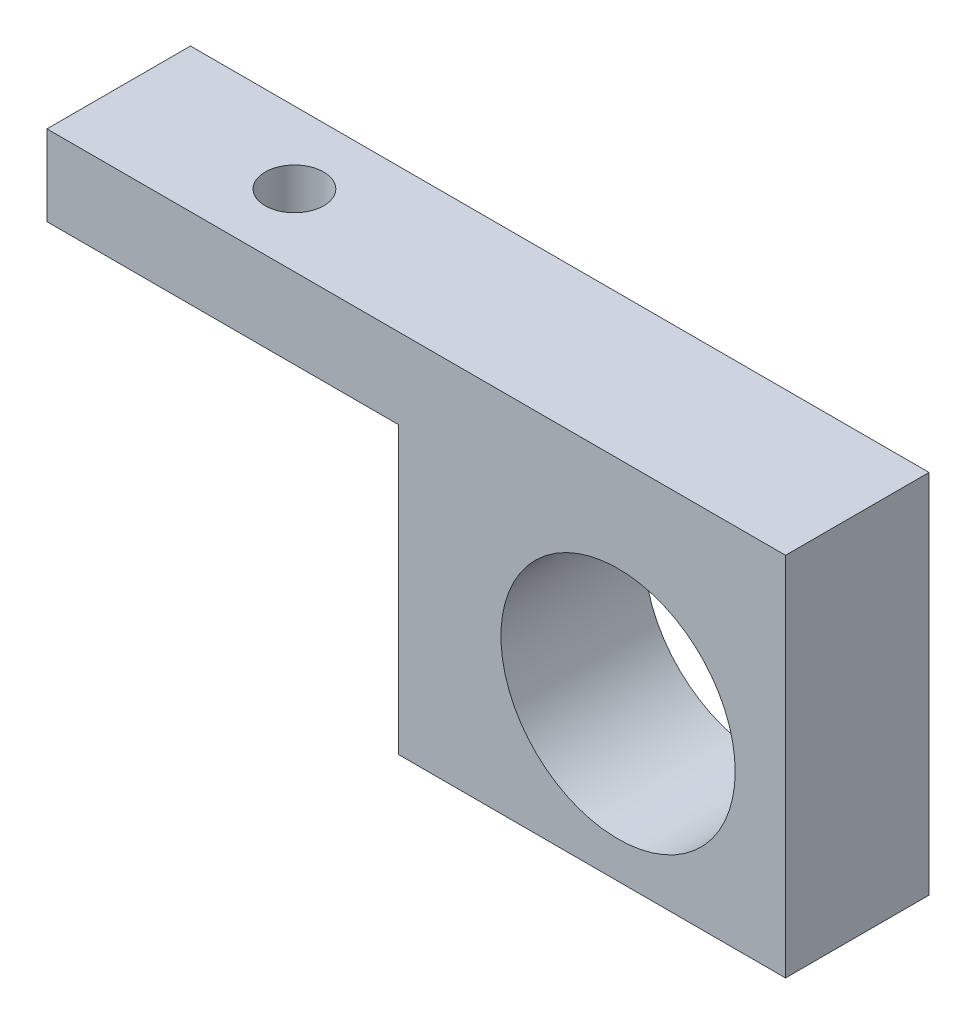
SolidWorks part; units mm, degrees
material "ABS"
ref_plane "Front Plane" through (0, 0, 0) normal (0, 0, 1) x (1, 0, 0)
ref_plane "Top Plane" through (0, 0, 0) normal (0, 1, 0) x (1, 0, 0)
ref_plane "Right Plane" through (0, 0, 0) normal (1, 0, 0) x (0, 0, -1)
sketch "Sketch1" plane through (0, 0, 0) normal (0, 0, 1) x (1, 0, 0)
  line L0 (-24, 15) -> (0, 15)
  line L1 (0, 15) -> (0, 0)
  line L2 (0, 0) -> (93, 0)
  line L3 (93, 0) -> (93, 102.7)
  line L4 (93, 102.7) -> (0, 102.7)
  line L5 (0, 102.7) -> (0, 30)
  line L6 (0, 30) -> (-24, 30)
  line L7 (-24, 30) -> (-24, 15)
  circle A0 centre (15, 10.5) radius 8
  circle A1 centre (70, 72) radius 11
  circle A2 centre (15, 10.5) radius 11
  dimension "D1" = 15
  dimension "D10" = 16
  dimension "D11" = 22
  dimension "D12" = 22
  dimension "D2" = 24
  dimension "D3" = 72.7
  dimension "D4" = 15
  dimension "D5" = 15
  dimension "D6" = 10.5
  dimension "D7" = 82.5061
  dimension "D8" = 72
  dimension "D9" = 93
extrude "Boss-Extrude1" add sketch "Sketch1" along normal blind 4.8 contours A2 L2 L3 L4 L5 L6 L7 L0 L1 A1 | L2 A2 A0 region at (44.5238, 51.0418, 0) region at (8.6656, 19.1141, 0)
sketch "Sketch2" plane through (0, 0, 4.8) normal (0, 0, 1) x (1, 0, 0)
  line L0 (93, 0) -> (93, 102.7) construction
  line L1 (48.1786, 92.7632) -> (93, 92.7632)
  line L2 (48.1786, 92.7632) -> (48.1786, 52.666)
  line L3 (48.1786, 52.666) -> (93, 52.666)
  line L4 (93, 92.7632) -> (93, 52.666)
  line L5 (48.1786, 92.7632) -> (93, 52.666) construction
  line L6 (48.1786, 52.666) -> (93, 92.7632) construction
  circle A0 centre (70, 72) radius 11
  circle A1 centre (70, 72) radius 4.15
  point P8 (70.5893, 72.7146)
  line M4 (93, 0) -> (93, 102.7)
  circle M10 centre (70, 72) radius 11
  dimension "D1" = 22
  dimension "D2" = 8.3
extrude "Boss-Extrude2" add sketch "Sketch2" along normal blind 8.2 contours L2 L3 L1 M4 M10 region at (70.5893, 92.1618, 4.8)
sketch "Sketch3" plane through (0, 0, 4.8) normal (0, 0, 1) x (1, 0, 0)
  line L1 (-24, 15) -> (0, 15)
  line L2 (-24, 15) -> (-24, 30)
  line L3 (-24, 30) -> (0, 30)
  line L4 (0, 15) -> (0, 30)
  line L5 (-24, 15) -> (0, 30) construction
  line L6 (-24, 30) -> (0, 15) construction
  line L7 (0, 0) -> (93, 0)
  line L8 (0, 0) -> (0, 52.666)
  line L9 (0, 52.666) -> (93, 52.666)
  line L10 (93, 0) -> (93, 52.666)
  line L11 (0, 0) -> (93, 52.666) construction
  line L12 (0, 52.666) -> (93, 0) construction
  circle A0 centre (15, 10.5) radius 8
  point P4 (-12, 22.5)
  point P11 (46.5, 26.333)
  circle M1 centre (15, 10.5) radius 8
  line M6 (0, 102.7) -> (0, 30)
  line M7 (0, 30) -> (-24, 30)
  line M8 (-24, 30) -> (-24, 15)
  line M9 (-24, 15) -> (0, 15)
  line M10 (0, 15) -> (0, 0)
  line M11 (0, 0) -> (93, 0)
  line M12 (93, 0) -> (93, 52.666)
  line M13 (93, 52.666) -> (48.1786, 52.666)
extrude "Boss-Extrude3" add sketch "Sketch3" along normal blind 5 contours L4 M9 M7 M8 | L9 L4 M6 M10 M11 M12 M13 M1 region at (-12, 22.5, 4.8) region at (47.8484, 27.0108, 4.8)
sketch "Sketch4" plane through (0, 83.2317, 0) normal (0, -1, 0) x (1, 0, 0)
  line L0 (0, 9.8) -> (0, 4.8) construction
  line L1 (0, 4.8) -> (48.1786, 4.8)
  line L2 (0, 4.8) -> (0, 45.3)
  line L3 (0, 45.3) -> (48.1786, 45.3)
  line L4 (48.1786, 4.8) -> (48.1786, 45.3)
  line L5 (0, 4.8) -> (48.1786, 45.3) construction
  line L6 (0, 45.3) -> (48.1786, 4.8) construction
  line L7 (0, 4.8) -> (48.1786, 4.8) construction
  line L8 (48.1786, 13) -> (48.1786, 9.8) construction
  line L9 (0, 0) -> (93, 0) construction
  line L10 (0, 45.3) -> (-5, 45.3)
  line L11 (0, 45.3) -> (0, 0)
  line L12 (0, 0) -> (-5, 0)
  line L13 (-5, 45.3) -> (-5, 0)
  line L14 (0, 45.3) -> (-5, 0) construction
  line L15 (0, 0) -> (-5, 45.3) construction
  circle A0 centre (13.9465, 30.3) radius 6.35
  circle A1 centre (13.9465, 23.3) radius 18.5
  circle A3 centre (29.4465, 23.3) radius 2
  circle A4 centre (21.6965, 9.8766) radius 2
  circle A5 centre (6.1965, 9.8766) radius 2
  point P10 (24.0893, 25.05)
  point P30 (-2.5, 22.65)
  arc M5 (5.039, 30.9329) -> (22.854, 30.9329) centre (13.9465, 30.3) ccw
  arc M7 (23.1854, 31.0672) -> (4.7077, 31.0672) centre (13.9465, 23.3) cw
  circle M9 centre (21.6965, 9.8766) radius 1.6
  circle M10 centre (6.1965, 9.8766) radius 1.6
  circle M11 centre (-1.5535, 23.3) radius 1.6
  circle M12 centre (6.1965, 36.7234) radius 1.6
  circle M13 centre (21.6965, 36.7234) radius 1.6
  circle M15 centre (27.3699, 31.05) radius 2.1
  circle M16 centre (0.5231, 31.05) radius 2.1
  circle M17 centre (13.9465, 7.8) radius 2.1
  circle M19 centre (13.9465, 23.3) radius 18.5
  dimension "D1" = 12.7
  dimension "D2" = 15
  dimension "D3" = 4
  dimension "D4" = 4
  dimension "D5" = 4
  dimension "D6" = 5
  dimension "D7" = 0
extrude "Boss-Extrude4" add sketch "Sketch4" along normal blind 5 contours L1 L4 L3 M19 | A0 L3 L2 A5 A4 A3 M12 M19 M16 M11 M13 M17 M15 M5 M7 | M5 M7 | M17 | A4 M9 | M9 | M10 | A5 M10 | M15 | L2 M16 | L2 L1 M19 region at (3.3557, 83.2317, 6.6306) region at (34.3643, 83.2317, 27.4815) region at (15.1399, 83.2317, 22.3686) region at (1.1393, 83.2317, 31.05) region at (19.7531, 83.2317, 9.8766) region at (4.2531, 83.2317, 9.8766) region at (21.6965, 83.2317, 9.8766) region at (6.1965, 83.2317, 9.8766) region at (27.3699, 83.2317, 31.05) region at (13.9465, 83.2317, 7.8)
sketch "Sketch5" plane through (48.1786, 0, 0) normal (1, 0, 0) x (0, 0, -1)
  line L0 (-45.3, 83.2317) -> (-13, 92.7632)
  line L1 (-13, 92.7632) -> (-4.8, 92.7632)
  line L2 (-4.8, 92.7632) -> (-4.8, 78.2317)
  line L3 (-4.8, 78.2317) -> (-45.3, 78.2317)
  line L4 (-45.3, 78.2317) -> (-45.3, 83.2317)
extrude "Boss-Extrude5" add sketch "Sketch5" against normal blind 5
sketch "Sketch6" plane through (0, 0, 4.8) normal (0, 0, 1) x (1, 0, 0)
  line L0 (0, 78.2317) -> (0, 52.666) construction
  line L1 (0, 78.2317) -> (48.1786, 78.2317)
  line L2 (0, 78.2317) -> (0, 52.666)
  line L3 (0, 52.666) -> (48.1786, 52.666)
  line L4 (48.1786, 78.2317) -> (48.1786, 52.666)
  line L5 (0, 78.2317) -> (48.1786, 52.666) construction
  line L6 (0, 52.666) -> (48.1786, 78.2317) construction
  line L7 (0, 78.2317) -> (48.1786, 78.2317) construction
  point P4 (24.0893, 65.4489)
extrude "Boss-Extrude6" add sketch "Sketch6" along normal up to surface (5 mm away) up to face at (20.6865, 27.5553, 9.8)
ref_plane "Plane1" through (3.9877, 7.5909, 34.4544) normal (0.9262, 0.2454, -0.2862) x (0.0581, -0.8429, -0.5349)
sketch "Sketch8" plane through (0, 30, 0) normal (0, 1, 0) x (1, 0, 0)
  line L0 (0, 0) -> (-24, -9.8)
  line L1 (-24, -9.8) -> (-24, 0)
  line L2 (-24, 0) -> (0, -9.8)
  circle A0 centre (-12, -4.9) radius 2
  dimension "D1" = 4
extrude "Cut-Extrude1" cut sketch "Sketch8" against normal through all contours A0
sketch "Sketch9" plane through (0, 0, 0) normal (0, 0, -1) x (-1, 0, 0)
  line L1 (0, 30) -> (-93, 30)
  line L2 (0, 30) -> (0, 102.7)
  line L3 (0, 102.7) -> (-93, 102.7)
  line L4 (-93, 30) -> (-93, 102.7)
extrude "Cut-Extrude2" cut sketch "Sketch9" against normal blind 100
sketch "Sketch10" plane through (0, 0, 9.8) normal (0, 0, 1) x (1, 0, 0)
  line L0 (93, 30) -> (-24, 30) construction
  line L1 (93, 0) -> (26.438, 0)
  line L2 (93, 0) -> (93, 30)
  line L3 (93, 30) -> (26.438, 30)
  line L4 (26.438, 0) -> (26.438, 30)
extrude "Cut-Extrude3" cut sketch "Sketch10" against normal blind 100
sketch "Sketch11" plane through (0, 0, 0) normal (0, 0, -1) x (-1, 0, 0)
  line L0 (24, 30) -> (24, 15) construction
  line L1 (0, 15) -> (24, 15)
  line L2 (0, 15) -> (0, 30)
  line L3 (0, 30) -> (24, 30)
  line L4 (24, 15) -> (24, 30)
  line L5 (-26.438, 30) -> (24, 30) construction
extrude "Boss-Extrude7" add sketch "Sketch11" along normal blind 12
sketch "Sketch13" plane through (-24, 0, 0) normal (-1, 0, 0) x (0, 0, 1)
  line L0 (9.8, 30) -> (9.8, 15) construction
  line L1 (-12, 30) -> (9.8, 30)
  line L2 (-12, 30) -> (-12, 25)
  line L3 (-12, 25) -> (9.8, 25)
  line L4 (9.8, 30) -> (9.8, 25)
  dimension "D1" = 5
extrude "Cut-Extrude4" cut sketch "Sketch13" against normal blind 200
sketch "Sketch15" plane through (0, 25, 0) normal (0, 1, 0) x (1, 0, 0)
  circle A0 centre (-12, 5.1) radius 2
  circle A1 centre (-12, -4.9) radius 2 construction
  dimension "D1" = 4
  dimension "D2" = 10
  dimension "D3" = 0
extrude "Cut-Extrude5" cut sketch "Sketch15" against normal blind 200
sketch "Sketch16" plane through (0, 25, 0) normal (0, 1, 0) x (1, 0, 0)
  line L1 (0, 0) -> (-24, 0)
  line L2 (0, 0) -> (0, 12)
  line L3 (0, 12) -> (-24, 12)
  line L4 (-24, 0) -> (-24, 12)
extrude "Cut-Extrude6" cut sketch "Sketch16" against normal blind 10
sketch "Sketch17" plane through (0, 0, 0) normal (0, 0, -1) x (-1, 0, 0)
  line L0 (24, 15) -> (24, 25) construction
  line L1 (0, 15) -> (24, 15)
  line L2 (0, 15) -> (0, 19.51)
  line L3 (0, 19.51) -> (24, 19.51)
  line L4 (24, 15) -> (24, 19.51)
  line L5 (0, 15) -> (24, 19.51) construction
  line L6 (0, 19.51) -> (24, 15) construction
  point P4 (12, 17.255)
  dimension "D1" = 4.51
extrude "Cut-Extrude7" cut sketch "Sketch17" against normal through all
